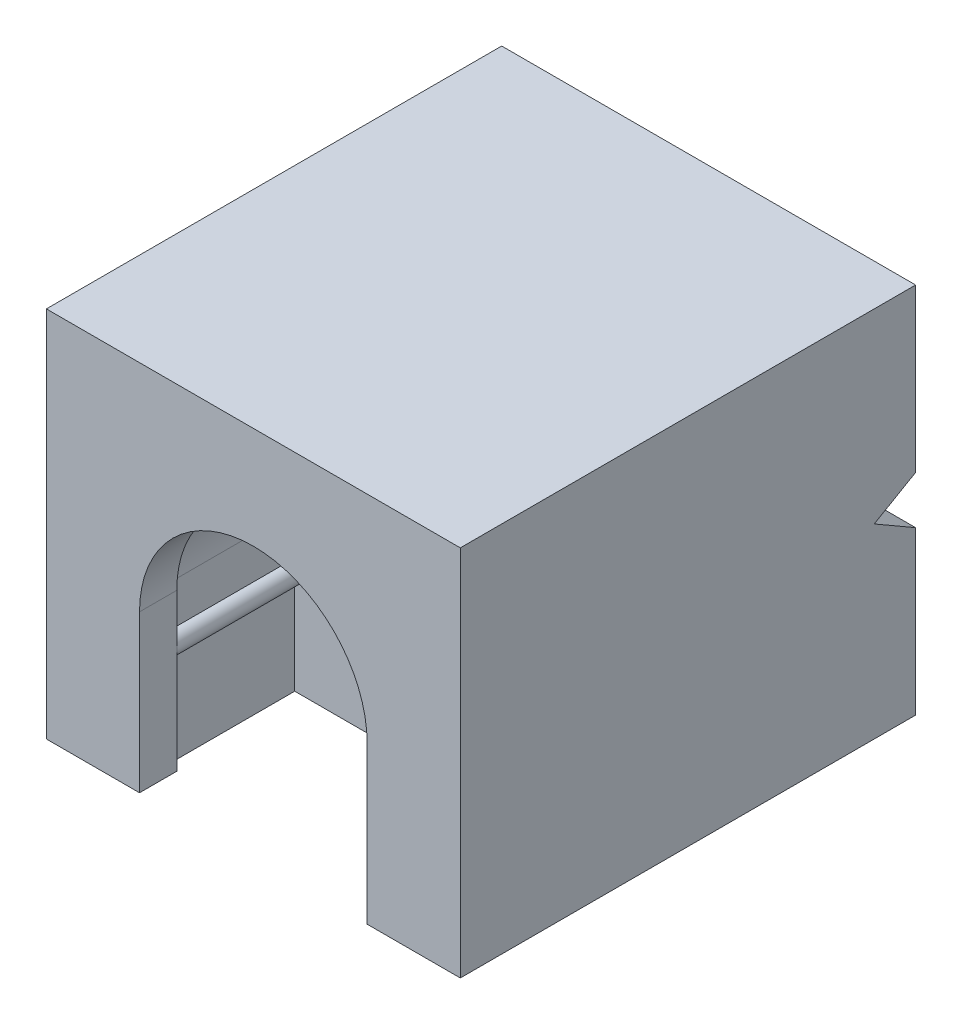
SolidWorks part; units mm, degrees
ref_plane "Front Plane" through (0, 0, 0) normal (0, 0, 1) x (1, 0, 0)
ref_plane "Top Plane" through (0, 0, 0) normal (0, 1, 0) x (1, 0, 0)
ref_plane "Right Plane" through (0, 0, 0) normal (1, 0, 0) x (0, 0, -1)
sketch "Sketch1" plane through (0, 0, 0) normal (0, 0, 1) x (1, 0, 0)
  line L0 (-3, 0) -> (-3, -3) construction
  line L1 (-3, -1.5) -> (-3, -3.7861)
  line L2 (-3, -3.7861) -> (-5, -3.7861)
  line L3 (-5, -3.7861) -> (-5, 5.2139)
  line L4 (-5, 5.2139) -> (5, 5.2139)
  line L5 (-3, -1) -> (-3, 0)
  line L6 (0, 0) -> (0, 5.2139) construction
  line L7 (3, 0) -> (3, -3) construction
  line L8 (3, -1) -> (3, 0)
  line L9 (5, -3.7861) -> (5, 5.2139)
  line L10 (3, -3.7861) -> (5, -3.7861)
  line L11 (3, -1.5) -> (3, -3.7861)
  circle A0 centre (0, 0) radius 3
  arc A1 (-3, -1) -> (-3, -1.5) centre (-3, -1.25) cw
  arc A2 (3, -1) -> (3, -1.5) centre (3, -1.25) ccw
  point P8 (-2.7689, -1.1546)
  point P21 (0, 5.2139)
  point P23 (2.7689, -1.1546)
  point P24 (-2.7728, -1.1454)
  point P25 (0, 3)
  point P26 (-2.7728, -1.1454)
  point P27 (-2.7728, -1.1454)
  point P28 (-2.7728, -1.1454)
  point P29 (-2.7689, -1.1546)
  point P30 (0, 0)
  dimension "D1" = 6
  dimension "D2" = 0.25
  dimension "D3" = 10
  dimension "D4" = 9
  dimension "D5" = 2
extrude "Boss-Extrude1" add sketch "Sketch1" along normal blind 4 contours L8 A2 A0 L11 L10 L9 L4 L3 L2 L1 A1 L5 region at (-3.1345, -2.643, 0)
sketch "Sketch2" plane through (0, 0, 0) normal (0, 0, 1) x (1, 0, 0)
  line L1 (5, 5.2139) -> (-5, 5.2139)
  line L2 (5, 5.2139) -> (5, -3.7861)
  line L3 (5, -3.7861) -> (-5, -3.7861)
  line L4 (-5, 5.2139) -> (-5, -3.7861)
extrude "Boss-Extrude2" add sketch "Sketch2" against normal blind 7
sketch "Sketch3" plane through (0, 0, -7) normal (0, 0, -1) x (-1, 0, 0)
  line L0 (-5, -3.7861) -> (5, 5.2139) construction
  line L1 (5, -3.7861) -> (-5, 5.2139) construction
  line L2 (-5, 5.2139) -> (5, 5.2139) construction
  circle A0 centre (0, 0.7139) radius 0.75
  point P8 (0, 0.7139)
  dimension "D1" = 1.5
  dimension "D2" = 4.5
extrude "Cut-Extrude1" cut sketch "Sketch3" against normal blind 6
sketch "Sketch4" plane through (5, 0, 0) normal (1, 0, 0) x (0, 0, -1)
  line L0 (7, -3.7861) -> (7, 5.2139) construction
  line L1 (7.5, -0.1521) -> (7.5, 1.58)
  line L2 (7.5, 1.58) -> (6, 0.7139)
  line L3 (6, 0.7139) -> (7.5, -0.1521)
  line L4 (6, 0.7139) -> (7, 0.7139) construction
  circle A0 centre (7, 0.7139) radius 0.5 construction
  dimension "D1" = 1
extrude "Cut-Extrude3" cut sketch "Sketch4" against normal up to surface (10 mm away) up to face at (-5, 0.7139, -1.5)
sketch "Sketch5" plane through (0, 0, 4) normal (0, 0, 1) x (1, 0, 0)
  line L0 (-2.75, 0) -> (2.75, 0) construction
  line L1 (-3, 0) -> (-3, -3.7861)
  line L2 (-2.75, 0) -> (-2.75, -3.7861)
  line L3 (-3, -3.7861) -> (3, -3.7861) construction
  line L4 (2.75, 0) -> (2.75, -3.7861)
  line L5 (-3, -3.7861) -> (-2.75, -3.7861)
  line L6 (2.75, -3.7861) -> (3, -3.7861)
  line L7 (3, 0) -> (3, -3.7861)
  arc A0 (-2.75, 0) -> (2.75, 0) centre (0, 0) cw
  arc A1 (-3, 0) -> (3, 0) centre (0, 0) cw
  circle A2 centre (0, 0) radius 3 construction
  point P4 (0, 0)
  line M2 (3, 0) -> (3, -1)
  arc M3 (3, -1) -> (3, -1.5) centre (3, -1.25) ccw
  arc M4 (-3, 0) -> (3, 0) centre (0, 0) cw
  arc M5 (3, -1) -> (3, -1.5) centre (3, -1.25) ccw
  line M6 (3, -1.5) -> (3, -3.7861)
  line M12 (-3, -3.7861) -> (-3, -1.5)
  arc M13 (-3, -1.5) -> (-3, -1) centre (-3, -1.25) ccw
  arc M14 (-3, 0) -> (3, 0) centre (0, 0) cw
  arc M15 (-3, -1.5) -> (-3, -1) centre (-3, -1.25) ccw
  line M16 (-3, -1) -> (-3, 0)
  arc M17 (-3, 0) -> (3, 0) centre (0, 0) cw
  dimension "D1" = 5.5
extrude "Boss-Extrude3" add sketch "Sketch5" against normal blind 1 contours L2 A0 L4 M5 M4 M3 M2 M17 M16 M15 M14 M13 | L5 L2 M12 M13 | L4 L6 M6 M5 | L4 L6 L7 A1 L1 L5 L2 A0 region at (0, 2.9265, 4) region at (-2.8734, -2.6155, 4) region at (2.8734, -2.6155, 4)
chamfer "Chamfer1" distance 0.1 angle 45 5 edges at (2.75, -2.518, 3) (0, 2.75, 3) (2.75, -0.625, 3) (-2.75, -0.625, 3) (-2.75, -2.518, 3)
